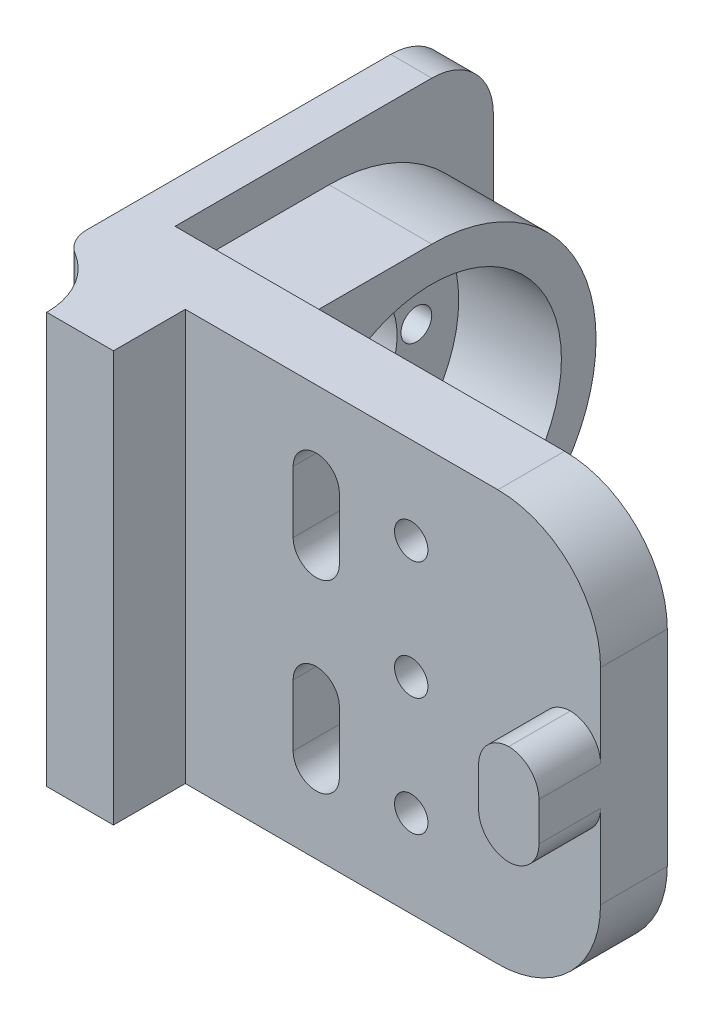
SolidWorks part; units mm, degrees
ref_plane "Plano frontal" through (0, 0, 0) normal (0, 0, 1) x (1, 0, 0)
ref_plane "Plano superior" through (0, 0, 0) normal (0, 1, 0) x (1, 0, 0)
ref_plane "Plano direito" through (0, 0, 0) normal (1, 0, 0) x (0, 0, -1)
sketch "Esboço1" plane through (0, 0, 0) normal (0, 0, 1) x (1, 0, 0)
  line L1 (35, -20) -> (-50, -20)
  line L2 (35, -20) -> (35, 20)
  line L3 (35, 20) -> (-50, 20)
  line L4 (-50, -20) -> (-50, 20)
  point P0 (0, 0)
  dimension "D1" = 40
  dimension "D2" = 35
  dimension "D3" = 50
extrude "Ressalto-extrusão1" add sketch "Esboço1" along normal blind 6.5
sketch "Esboço2" plane through (0, 0, 6.5) normal (0, 0, 1) x (1, 0, 0)
  line L0 (-50, -20) -> (35, -20) construction
  line L1 (-50, 20) -> (-38.5, 20)
  line L2 (-50, 20) -> (-50, -20)
  line L3 (-50, -20) -> (-38.5, -20)
  line L4 (-38.5, 20) -> (-38.5, -20)
  dimension "D1" = 11.5
extrude "Ressalto-extrusão2" add sketch "Esboço2" along normal up to surface (7 mm away) up to face at (-7.5, 0, 6.5)
sketch "Esboço3" plane through (0, 0, 6.5) normal (0, 0, 1) x (1, 0, 0)
  circle A0 centre (-16.5, -11.5) radius 1.625 construction
  circle A1 centre (-16.5, 0) radius 1.625 construction
  circle A2 centre (-16.5, 11.5) radius 1.625 construction
  circle A3 centre (-16.5, -11.5) radius 1.625
  circle A4 centre (-16.5, 0) radius 1.625
  circle A5 centre (-16.5, 11.5) radius 1.625
extrude "Corte-extrusão1" cut sketch "Esboço3" against normal through all both and the other way through all
sketch "Esboço6" plane through (0, 0, 0) normal (0, 0, -1) x (-1, 0, 0)
  circle A0 centre (16.5, -11.5) radius 3.625
  circle A1 centre (16.5, 0) radius 3.625
  circle A2 centre (16.5, 11.5) radius 3.625
  dimension "D1" = 7.25
extrude "Corte-extrusão3" cut sketch "Esboço6" against normal blind 3
sketch "Esboço7" plane through (0, 0, 0) normal (0, 0, -1) x (-1, 0, 0)
  line L0 (-35, 20) -> (50, 20) construction
  line L1 (50, -20) -> (46, -20)
  line L2 (50, -20) -> (50, 20)
  line L3 (50, 20) -> (46, 20)
  line L4 (46, -20) -> (46, 20)
  dimension "D1" = 4
extrude "Ressalto-extrusão4" add sketch "Esboço7" along normal blind 31
sketch "Esboço8" plane through (-46, 0, 0) normal (1, 0, 0) x (0, 0, -1)
  line L0 (31, 20) -> (31, -20) construction
  line L1 (0, -20) -> (0, 20) construction
  line L2 (0, -20) -> (0, 20)
  line L3 (0, 0) -> (15, 0) construction
  line L5 (15, -16) -> (0, -16)
  line L6 (0, -16) -> (0, 16)
  line L7 (0, 16) -> (15, 16)
  circle A0 centre (15, 0) radius 12.625
  arc A1 (15, -16) -> (15, 16) centre (15, 0) ccw
  dimension "D2" = 25.25
  dimension "D1" = 15
extrude "Ressalto-extrusão8" add sketch "Esboço8" along normal blind 10 contours A1 L7 L2 A0 L6 L5 region at (-46, 0, -0.4455)
sketch "Esboço10" plane through (-46, 0, 0) normal (1, 0, 0) x (0, 0, -1)
  line L0 (15, 0) -> (15, -8.5) construction
  circle A0 centre (15, 0) radius 6.625
  circle A1 centre (15, -8.5) radius 1.5
  circle A2 centre (6.5, 0) radius 1.5
  circle A3 centre (15, 8.5) radius 1.5
  circle A4 centre (23.5, 0) radius 1.5
  point P14 (15, 0)
  dimension "D1" = 13.25
  dimension "D2" = 3
  dimension "D3" = 8.5
  dimension "D4" = 4
extrude "Corte-extrusão4" cut sketch "Esboço10" against normal through all both and the other way through all
fillet "Filete1" radius 6 2 edges at (-48, -20, -31) (-48, 20, -31)
sketch "Esboço11" plane through (0, 20, 0) normal (0, 1, 0) x (1, 0, 0)
  line L1 (-38.5, -13.5) -> (-50, -13.5) construction
  line L3 (-38.5, -13.5) -> (-38.5, -6.5) construction
  line L4 (-45, -22.0811) -> (-45, -13.5) construction
  line L5 (-50, -13.5) -> (-50, 25) construction
  line L6 (-38.5, -6.5) -> (-50, -6.5) construction
  line L7 (-50, -6.5) -> (-50, -13.5)
  line L8 (-50, -13.5) -> (-45, -13.5)
  arc A0 (-45, -13.5) -> (-50, -6.5) centre (-52.4, -13.5) ccw
  dimension "D1" = 6.5
extrude "Corte-extrusão5" cut sketch "Esboço11" against normal up to surface (40 mm away) up to face at (-24.875, -20, -1.25)
fillet "Filete3" radius 3 1 edges at (-50, 0, 6.5)
sketch "Esboço13" plane through (0, 0, 6.5) normal (0, 0, 1) x (1, 0, 0)
  line L2 (-28, -6) -> (-28, -12)
  line L3 (-23.5, -12) -> (-23.5, -6)
  line L4 (-28, -6) -> (-28, -12)
  line L5 (-23.5, -12) -> (-23.5, -6)
  line L6 (-23.5, 6) -> (-23.5, 12)
  line L7 (-28, 12) -> (-28, 6)
  line L8 (-23.5, 6) -> (-23.5, 12)
  line L9 (-28, 12) -> (-28, 6)
  arc A2 (-23.5, -6) -> (-28, -6) centre (-25.75, -6) ccw
  arc A3 (-28, -12) -> (-23.5, -12) centre (-25.75, -12) ccw
  arc A4 (-23.5, -6) -> (-28, -6) centre (-25.75, -6) ccw
  arc A5 (-28, -12) -> (-23.5, -12) centre (-25.75, -12) ccw
  arc A6 (-28, 6) -> (-23.5, 6) centre (-25.75, 6) ccw
  arc A7 (-23.5, 12) -> (-28, 12) centre (-25.75, 12) ccw
  arc A8 (-28, 6) -> (-23.5, 6) centre (-25.75, 6) ccw
  arc A9 (-23.5, 12) -> (-28, 12) centre (-25.75, 12) ccw
  dimension "D1" = 0
  dimension "D2" = 0
extrude "Corte-extrusão7" cut sketch "Esboço13" against normal through all both and the other way through all
sketch "Esboço14" plane through (0, 0, 6.5) normal (0, 0, 1) x (1, 0, 0)
  line L0 (-4, 3) -> (-4, -3) construction
  line L1 (-2, -5) -> (0, -5) construction
  line L2 (2, -3) -> (2, 3) construction
  line L3 (0, 5) -> (-2, 5) construction
  line L4 (-4, 3) -> (-4, -3) construction
  line L5 (-2, -5) -> (0, -5) construction
  line L6 (2, -3) -> (2, 3) construction
  line L7 (0, 5) -> (-2, 5) construction
  line L18 (-2, 3) -> (0, -3) construction
  line L19 (-3.9375, 0) -> (-4, 0) construction
  line L20 (-2, -3) -> (0, 3) construction
  line L21 (1.9375, -4.875) -> (-3.9375, -4.875)
  line L22 (1.9375, -4.875) -> (1.9375, 4.875)
  line L23 (1.9375, 4.875) -> (-3.9375, 4.875)
  line L24 (-3.9375, -4.875) -> (-3.9375, 4.875)
  line L25 (1.9375, -4.875) -> (-3.9375, 4.875) construction
  line L26 (1.9375, 4.875) -> (-3.9375, -4.875) construction
  line L27 (1.9375, 0) -> (2, 0) construction
  line L28 (-1, -5) -> (-1, -4.875) construction
  line L29 (-1, 4.875) -> (-1, 5) construction
  arc A0 (-2, 5) -> (-4, 3) centre (-2, 3) ccw construction
  arc A1 (-2, 5) -> (-4, 3) centre (-2, 3) ccw construction
  arc A2 (-4, -3) -> (-2, -5) centre (-2, -3) ccw construction
  arc A3 (0, -5) -> (2, -3) centre (0, -3) ccw construction
  arc A4 (2, 3) -> (0, 5) centre (0, 3) ccw construction
  arc A5 (-4, -3) -> (-2, -5) centre (-2, -3) ccw construction
  arc A6 (0, -5) -> (2, -3) centre (0, -3) ccw construction
  arc A7 (2, 3) -> (0, 5) centre (0, 3) ccw construction
  point P11 (-1, 0)
  dimension "D1" = 0.125
  dimension "D2" = 0.125
extrude "Ressalto-extrusão9" add sketch "Esboço14" along normal offset from surface (6 mm away) 1 up to face at (-41.75, 0, 13.5)
fillet "Filete4" radius 3 4 edges at (-3.9375, 4.875, 9.5) (-3.9375, -4.875, 9.5) (1.9375, 4.875, 9.5) (1.9375, -4.875, 9.5)
sketch "Esboço15" plane through (0, 0, 6.5) normal (0, 0, 1) x (1, 0, 0)
  line L0 (1.9375, 20) -> (35, 20)
  line L1 (35, 20) -> (-38.5, 20) construction
  line L2 (35, 20) -> (35, -20)
  line L3 (35, -20) -> (1.9375, -20)
  line L4 (-38.5, -20) -> (35, -20) construction
  line L5 (1.9375, -20) -> (1.9375, 20)
  line L7 (1.9375, -1.875) -> (1.9375, 1.875) construction
extrude "Corte-extrusão8" cut sketch "Esboço15" against normal through all both and the other way through all
fillet "Filete5" radius 10 2 edges at (1.9375, 20, 3.25) (1.9375, -20, 3.25)
equation "\"3d\"= 0.25mm"
equation "\"D1@Esboço14\"=\"3d\"/2"
equation "\"D2@Esboço14\"=\"3d\"/2"
equation "\"D1@Esboço6\"=7mm + \"3d\""
equation "\"D2@Esboço8\"=25.00mm + \"3d\""
equation "\"D1@Esboço10\"= 13.00mm + \"3d\""
